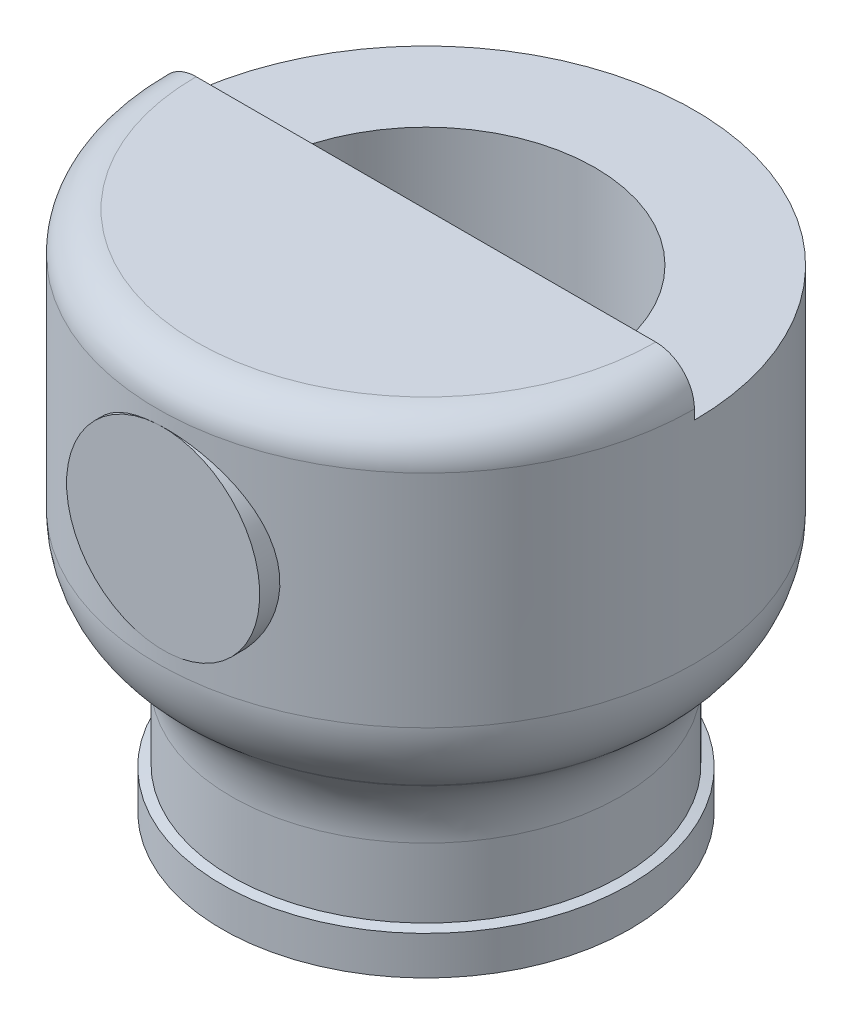
SolidWorks part; units mm, degrees
ref_plane "Front Plane" through (0, 0, 0) normal (0, 0, 1) x (1, 0, 0)
ref_plane "Top Plane" through (0, 0, 0) normal (0, 1, 0) x (1, 0, 0)
ref_plane "Right Plane" through (0, 0, 0) normal (1, 0, 0) x (0, 0, -1)
sketch "Sketch1" plane through (0, 0, 0) normal (0, 0, 1) x (1, 0, 0)
  line L0 (2.7649, 7.8218) -> (2.7649, 58.3592) construction
  line L1 (20.9, 0) -> (23.8716, 0)
  line L2 (23.8716, 0) -> (23.8716, 4)
  line L3 (23.8716, 4) -> (22.9, 4.2367)
  line L4 (22.9, 4.2367) -> (22.9, 11.4043)
  line L6 (20.9, 0) -> (20.9, 14)
  line L12 (19.9, 15) -> (2.7649, 15)
  line L17 (26.4721, 19.0648) -> (26.9883, 19.4979)
  line L18 (30.5604, 27.1583) -> (30.5604, 50)
  line L20 (26.5604, 54) -> (2.7649, 54)
  line L22 (2.7649, 15) -> (2.7649, 54)
  arc A1 (30.5604, 50) -> (26.5604, 54) centre (26.5604, 50) ccw
  arc A2 (26.4721, 19.0648) -> (22.9, 11.4043) centre (32.9, 11.4043) ccw
  arc A3 (26.9883, 19.4979) -> (30.5604, 27.1583) centre (20.5604, 27.1583) ccw
  arc A6 (20.9, 14) -> (19.9, 15) centre (19.9, 14) ccw
  point P11 (22.9, 54)
  point P28 (28.5604, 23.4279)
  point P31 (20.9, 17)
  dimension "D9" = 4
  dimension "D16" = 10
  dimension "D19" = 1
  dimension "D2" = 4
  dimension "D3" = 1
  dimension "D6" = 2
  dimension "D7" = 2.9716
  dimension "D11" = 15
  dimension "D15" = 10
revolve "Revolve1" add sketch "Sketch1" angle 360 about L0
ref_plane "Plane1" through (0, 4, 0) normal (0, 1, 0) x (1, 0, 0)
sketch "Sketch3" plane through (0, 0, 0) normal (0, 0, 1) x (1, 0, 0)
  point P0 (1.2404, 19.1989)
ref_point "Point1"
ref_plane "Plane2" through (0, 0, 22.9) normal (0, 0, 1) x (1, 0, 0)
ref_plane "Plane3" through (0, 0, 27.7955) normal (0, 0, 1) x (1, 0, 0)
ref_plane "Plane4" through (0, 54, 0) normal (0, 1, 0) x (1, 0, 0)
sketch "Sketch9" plane through (0, 54, 0) normal (0, 1, 0) x (1, 0, 0)
  line L0 (-25.2351, 0) -> (30.7649, 0)
  arc A0 (30.7649, 0) -> (-25.2351, 0) centre (2.7649, 0) ccw
  circle A3 centre (2.7649, 0) radius 23.7955 construction
  dimension "D1" = 56
  dimension "D3" = 28
  dimension "D4" = 0
sketch "Sketch10" plane through (0, 0, 27.7955) normal (0, 0, 1) x (1, 0, 0)
  line L0 (30.5604, 27.1583) -> (-25.0306, 27.1583) construction
  circle A0 centre (3.3463, 38.6583) radius 10
  dimension "D1" = 20
  dimension "D2" = 11.5
extrude "Boss-Extrude1" add sketch "Sketch10" against normal blind 5
ref_plane "Plane5" through (0, 17, 0) normal (0, 1, 0) x (1, 0, 0)
sketch "Sketch11" plane through (0, 17, 0) normal (0, 1, 0) x (1, 0, 0)
  line L0 (-14.7351, 0) -> (20.2649, 0)
  arc A1 (-14.7351, 0) -> (20.2649, 0) centre (2.7649, 0) cw
  circle A2 centre (2.7649, 0) radius 20.9233 construction
  dimension "D2" = 0
  dimension "D1" = 35
extrude "Cut-Extrude3" cut sketch "Sketch11" against normal blind 20 and the other way blind 45
ref_plane "Plane6" through (0, 0, -27.7955) normal (0, 0, -1) x (-1, 0, 0)
sketch "Sketch12" plane through (0, 0, 27.7955) normal (0, 0, 1) x (1, 0, 0)
  line L0 (30.5604, 50) -> (-25.0306, 50) construction
  line L1 (-26.9971, 52.5) -> (33.0029, 52.5)
  line L2 (-26.9971, 52.5) -> (-26.9971, 49.5)
  line L3 (-26.9971, 49.5) -> (33.0029, 49.5)
  line L4 (33.0029, 52.5) -> (33.0029, 49.5)
  line L5 (-26.9971, 52.5) -> (33.0029, 49.5) construction
  line L6 (-26.9971, 49.5) -> (33.0029, 52.5) construction
  point P0 (3.0029, 51)
  dimension "D1" = 3
  dimension "D2" = 1
  dimension "D3" = 60
extrude "Cut-Extrude5" cut sketch "Sketch9" against normal blind 5
sketch "Sketch13" plane through (0, 0, 0) normal (0, 0, -1) x (-1, 0, 0)
  line L0 (25.0306, 49) -> (14.7351, 49) construction
  line L1 (17.0306, 53) -> (22.0306, 53)
  line L2 (17.0306, 53) -> (17.0306, 50)
  line L3 (17.0306, 50) -> (22.0306, 50)
  line L4 (22.0306, 53) -> (22.0306, 50)
  line L5 (17.0306, 53) -> (22.0306, 50) construction
  line L6 (17.0306, 50) -> (22.0306, 53) construction
  line L7 (25.0306, 49) -> (25.0306, 50) construction
  line L8 (-30.5604, 50) -> (-30.5604, 49) construction
  line L9 (-27.5604, 52.75) -> (-22.5604, 52.75)
  line L10 (-27.5604, 52.75) -> (-27.5604, 49.75)
  line L11 (-27.5604, 49.75) -> (-22.5604, 49.75)
  line L12 (-22.5604, 52.75) -> (-22.5604, 49.75)
  line L13 (-27.5604, 52.75) -> (-22.5604, 49.75) construction
  line L14 (-27.5604, 49.75) -> (-22.5604, 52.75) construction
  line L15 (-20.2649, 49) -> (-30.5604, 49) construction
  point P0 (19.5306, 51.5)
  point P7 (-25.0604, 51.25)
  dimension "D1" = 2.5
  dimension "D2" = 3
  dimension "D3" = 3
  dimension "D4" = 5
  dimension "D5" = 5
  dimension "D6" = 3
  dimension "D7" = 3
  dimension "D8" = 2.25
